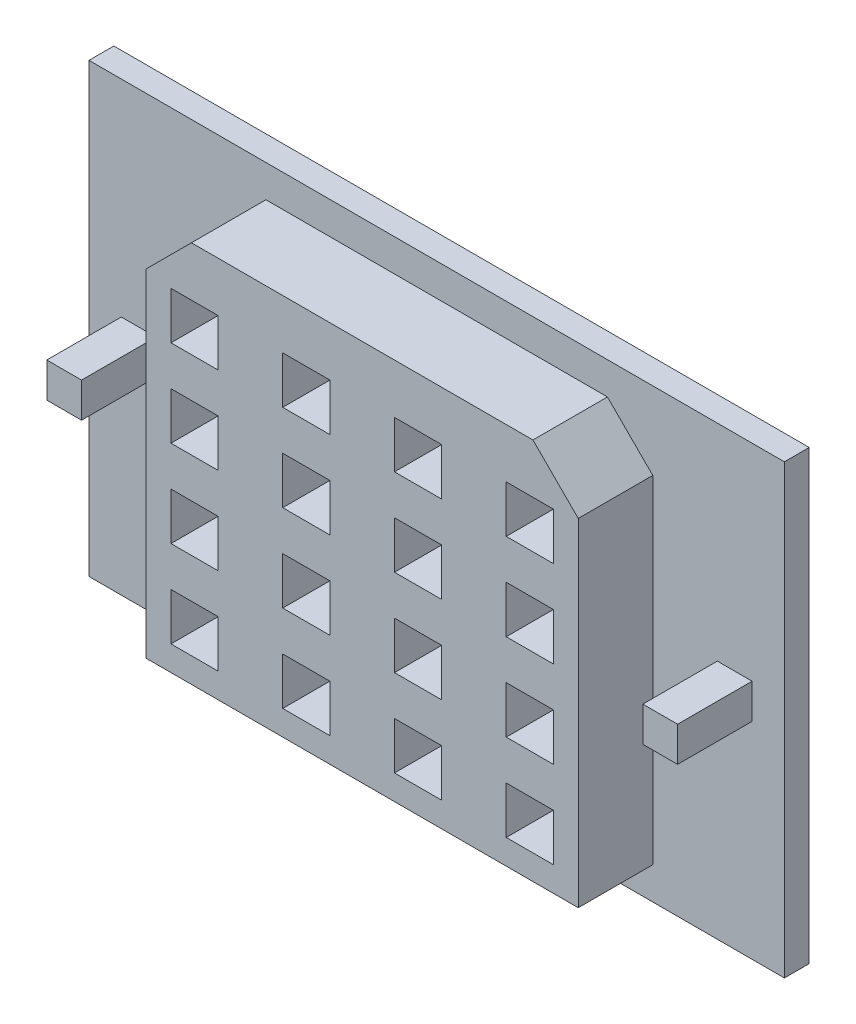
SolidWorks part; units mm, degrees
ref_plane "Front Plane" through (0, 0, 0) normal (0, 0, 1) x (1, 0, 0)
ref_plane "Top Plane" through (0, 0, 0) normal (0, 1, 0) x (1, 0, 0)
ref_plane "Right Plane" through (0, 0, 0) normal (1, 0, 0) x (0, 0, -1)
sketch "Sketch1" plane through (0, 0, 0) normal (0, 0, 1) x (1, 0, 0)
  line L1 (-15.2366, 7.7588) -> (12.7634, 7.7588)
  line L2 (-15.2366, 7.7588) -> (-15.2366, -10.2412)
  line L3 (-15.2366, -10.2412) -> (12.7634, -10.2412)
  line L4 (12.7634, 7.7588) -> (12.7634, -10.2412)
  dimension "D1" = 28
  dimension "D2" = 18
extrude "Boss-Extrude1" add sketch "Sketch1" along normal blind 1
sketch "Sketch2" plane through (0, 0, 1) normal (0, 0, 1) x (1, 0, 0)
  line L0 (-1.2366, 7.7588) -> (-1.2366, -10.2412) construction
  line L1 (12.7634, 7.7588) -> (-15.2366, 7.7588) construction
  line L2 (-15.2366, -10.2412) -> (12.7634, -10.2412) construction
  line L3 (-15.2366, -1.2412) -> (12.7634, -1.2412) construction
  line L4 (-15.2366, 7.7588) -> (-15.2366, -10.2412) construction
  line L5 (12.7634, -10.2412) -> (12.7634, 7.7588) construction
  line L7 (-14.2366, -0.2412) -> (-12.2366, -0.2412) construction
  line L8 (-14.2366, -0.2412) -> (-14.2366, -2.2412) construction
  line L9 (-14.2366, -2.2412) -> (-12.2366, -2.2412) construction
  line L10 (-12.2366, -0.2412) -> (-12.2366, -2.2412) construction
  line L11 (11.7634, -0.2412) -> (9.7634, -0.2412) construction
  line L12 (11.7634, -0.2412) -> (11.7634, -2.2412) construction
  line L13 (11.7634, -2.2412) -> (9.7634, -2.2412) construction
  line L14 (9.7634, -0.2412) -> (9.7634, -2.2412) construction
  line L15 (-10.2366, 6.7588) -> (7.7634, 6.7588) construction
  line L16 (-10.2366, 6.7588) -> (-10.2366, -9.2412) construction
  line L17 (-10.2366, -9.2412) -> (7.7634, -9.2412) construction
  line L18 (7.7634, 6.7588) -> (7.7634, -9.2412) construction
  line L22 (11.4634, -0.5412) -> (10.0634, -0.5412)
  line L23 (10.0634, -0.5412) -> (10.0634, -1.9412)
  line L24 (11.4634, -1.9412) -> (10.0634, -1.9412)
  line L25 (11.4634, -0.5412) -> (11.4634, -1.9412)
  line L30 (-13.9366, -0.5412) -> (-12.5366, -0.5412)
  line L31 (-12.5366, -0.5412) -> (-12.5366, -1.9412)
  line L32 (-13.9366, -1.9412) -> (-12.5366, -1.9412)
  line L33 (-13.9366, -0.5412) -> (-13.9366, -1.9412)
  line L34 (5.7634, 6.7588) -> (7.7634, 4.7588) construction
  line L35 (-10.2366, 4.7588) -> (-8.2366, 6.7588) construction
  line L36 (-8.1124, 6.4588) -> (5.6391, 6.4588)
  line L37 (7.4634, 4.6345) -> (7.4634, -8.9412)
  line L38 (-9.9366, -8.9412) -> (7.4634, -8.9412)
  line L39 (-9.9366, 4.6345) -> (-9.9366, -8.9412)
  line L40 (-9.9366, 4.6345) -> (-8.1124, 6.4588)
  line L41 (5.6391, 6.4588) -> (7.4634, 4.6345)
  line L42 (7.4634, 6.4588) -> (7.4634, -8.9412) construction
  line L43 (-9.9366, 6.4588) -> (7.4634, 6.4588) construction
  line L44 (-9.9366, 6.4588) -> (-9.9366, -8.9412) construction
  line L45 (-10.0245, 4.5466) -> (-8.0245, 6.5466) construction
  line L46 (5.5512, 6.5466) -> (7.5512, 4.5466) construction
  point P20 (-12.2366, -1.2412)
  point P21 (9.7634, -1.2412)
  point P26 (-1.2366, 6.7588)
  point P27 (-10.2366, -1.2412)
  point P40 (0, 0)
  point P41 (0, 0)
  point P42 (0, 0)
  point P43 (0, 0)
  point P44 (7.8533, 6.7588)
  point P54 (0, 0)
  dimension "D1" = 2
  dimension "D2" = 2
  dimension "D3" = 0
  dimension "D4" = 2
  dimension "D5" = 2
  dimension "D6" = 0
  dimension "D7" = 18
  dimension "D8" = 16
  dimension "D9" = 0
  dimension "D10" = 0
  dimension "D12" = 2
  dimension "D13" = 2
  dimension "D11" = 135
  dimension "D16" = 135
  dimension "D17" = 2
  dimension "D18" = 2
  dimension "D14" = 0.3
  dimension "D15" = 0.3
  dimension "D19" = 0.3
  dimension "D20" = 0.3
extrude "Boss-Extrude3" add sketch "Sketch2" along normal blind 3
sketch "Sketch3" plane through (0, 0, 4) normal (0, 0, 1) x (1, 0, 0)
  line L0 (1.9634, 2.5588) -> (0.0634, 2.5588)
  line L13 (6.4634, 2.5588) -> (4.5634, 2.5588)
  line L14 (6.4634, 2.5588) -> (6.4634, 4.4588)
  line L15 (6.4634, 4.4588) -> (4.5634, 4.4588)
  line L16 (4.5634, 2.5588) -> (4.5634, 4.4588)
  line L17 (1.9634, 2.5588) -> (1.9634, 4.4588)
  line L18 (1.9634, 4.4588) -> (0.0634, 4.4588)
  line L19 (0.0634, 2.5588) -> (0.0634, 4.4588)
  line L20 (-2.5366, 2.5588) -> (-4.4366, 2.5588)
  line L21 (-2.5366, 2.5588) -> (-2.5366, 4.4588)
  line L22 (-2.5366, 4.4588) -> (-4.4366, 4.4588)
  line L23 (-4.4366, 2.5588) -> (-4.4366, 4.4588)
  line L24 (-7.0366, 2.5588) -> (-8.9366, 2.5588)
  line L25 (-7.0366, 2.5588) -> (-7.0366, 4.4588)
  line L26 (-7.0366, 4.4588) -> (-8.9366, 4.4588)
  line L27 (-8.9366, 2.5588) -> (-8.9366, 4.4588)
  line L28 (1.9634, -0.9412) -> (0.0634, -0.9412)
  line L29 (1.9634, -0.9412) -> (1.9634, 0.9588)
  line L30 (1.9634, 0.9588) -> (0.0634, 0.9588)
  line L31 (0.0634, -0.9412) -> (0.0634, 0.9588)
  line L32 (-2.5366, -0.9412) -> (-4.4366, -0.9412)
  line L33 (-2.5366, -0.9412) -> (-2.5366, 0.9588)
  line L34 (-2.5366, 0.9588) -> (-4.4366, 0.9588)
  line L35 (-4.4366, -0.9412) -> (-4.4366, 0.9588)
  line L36 (-7.0366, -0.9412) -> (-8.9366, -0.9412)
  line L37 (-7.0366, -0.9412) -> (-7.0366, 0.9588)
  line L38 (-7.0366, 0.9588) -> (-8.9366, 0.9588)
  line L39 (-8.9366, -0.9412) -> (-8.9366, 0.9588)
  line L40 (1.9634, -4.4412) -> (0.0634, -4.4412)
  line L41 (1.9634, -4.4412) -> (1.9634, -2.5412)
  line L42 (1.9634, -2.5412) -> (0.0634, -2.5412)
  line L43 (0.0634, -4.4412) -> (0.0634, -2.5412)
  line L44 (-2.5366, -4.4412) -> (-4.4366, -4.4412)
  line L45 (-2.5366, -4.4412) -> (-2.5366, -2.5412)
  line L46 (-2.5366, -2.5412) -> (-4.4366, -2.5412)
  line L47 (-4.4366, -4.4412) -> (-4.4366, -2.5412)
  line L48 (-7.0366, -4.4412) -> (-8.9366, -4.4412)
  line L49 (-7.0366, -4.4412) -> (-7.0366, -2.5412)
  line L50 (-7.0366, -2.5412) -> (-8.9366, -2.5412)
  line L51 (-8.9366, -4.4412) -> (-8.9366, -2.5412)
  line L52 (1.9634, -7.9412) -> (0.0634, -7.9412)
  line L53 (1.9634, -7.9412) -> (1.9634, -6.0412)
  line L54 (1.9634, -6.0412) -> (0.0634, -6.0412)
  line L55 (0.0634, -7.9412) -> (0.0634, -6.0412)
  line L56 (-2.5366, -7.9412) -> (-4.4366, -7.9412)
  line L57 (-2.5366, -7.9412) -> (-2.5366, -6.0412)
  line L58 (-2.5366, -6.0412) -> (-4.4366, -6.0412)
  line L59 (-4.4366, -7.9412) -> (-4.4366, -6.0412)
  line L60 (-7.0366, -7.9412) -> (-8.9366, -7.9412)
  line L61 (-7.0366, -7.9412) -> (-7.0366, -6.0412)
  line L62 (-7.0366, -6.0412) -> (-8.9366, -6.0412)
  line L63 (-8.9366, -7.9412) -> (-8.9366, -6.0412)
  line L64 (6.4634, -0.9412) -> (4.5634, -0.9412)
  line L65 (6.4634, -0.9412) -> (6.4634, 0.9588)
  line L66 (6.4634, 0.9588) -> (4.5634, 0.9588)
  line L67 (4.5634, -0.9412) -> (4.5634, 0.9588)
  line L68 (6.4634, -4.4412) -> (4.5634, -4.4412)
  line L69 (6.4634, -4.4412) -> (6.4634, -2.5412)
  line L70 (6.4634, -2.5412) -> (4.5634, -2.5412)
  line L71 (4.5634, -4.4412) -> (4.5634, -2.5412)
  line L72 (6.4634, -7.9412) -> (4.5634, -7.9412)
  line L73 (6.4634, -7.9412) -> (6.4634, -6.0412)
  line L74 (6.4634, -6.0412) -> (4.5634, -6.0412)
  line L75 (4.5634, -7.9412) -> (4.5634, -6.0412)
  line L76 (-9.9366, -8.9412) -> (7.4634, -8.9412) construction
  line L77 (-9.9366, 4.6345) -> (-9.9366, -8.9412) construction
  line L78 (7.4634, -8.9412) -> (7.4634, 4.6345) construction
  line L79 (5.6391, 6.4588) -> (-8.1124, 6.4588) construction
  line L80 (-9.9366, 4.6345) -> (-9.9366, -8.9412) construction
  point P0 (5.5134, -7.9412)
  point P67 (-8.9366, -6.9912)
  dimension "D1" = 1.9
  dimension "D2" = 1.9
  dimension "D5" = 1
  dimension "D6" = 1
  dimension "D7" = 1
  dimension "D8" = 2
  dimension "D9" = 1
  dimension "D3" = 4
  dimension "D4" = 4
extrude "Cut-Extrude1" cut sketch "Sketch3" against normal through all both and the other way through all
